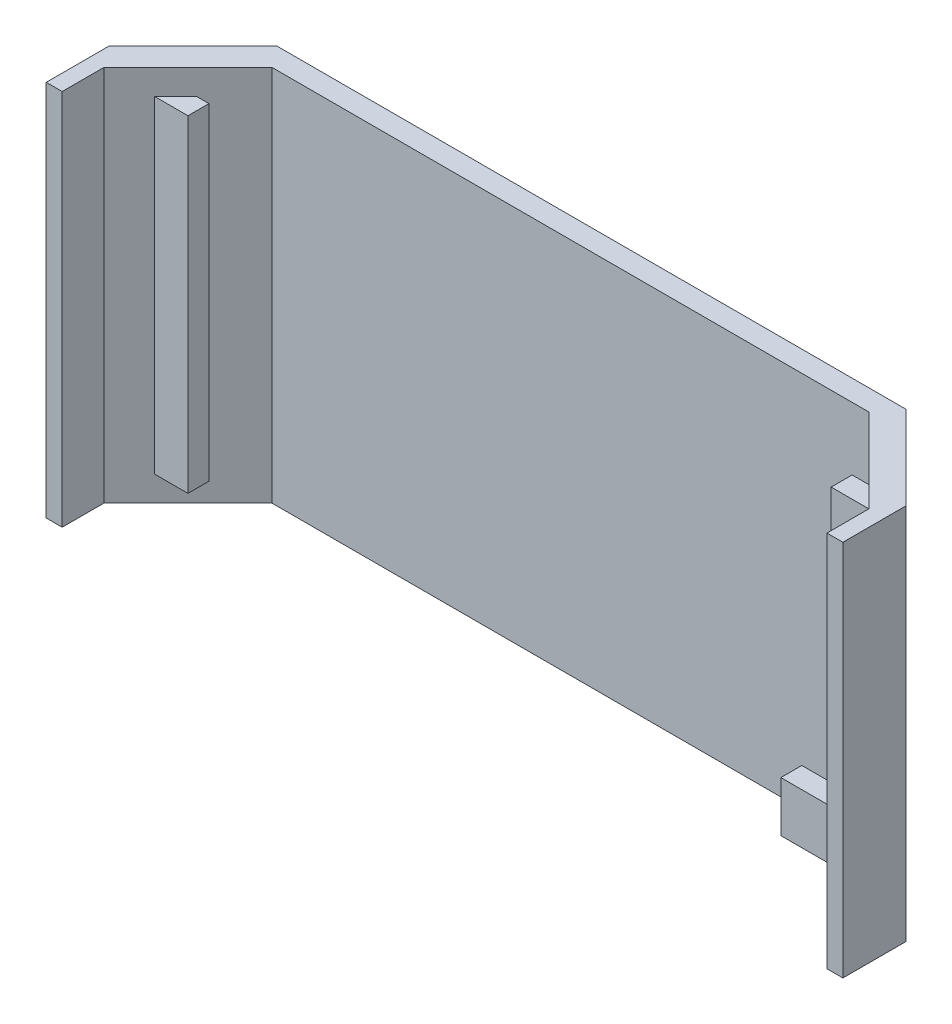
SolidWorks part; units mm, degrees
ref_plane "Front Plane" through (0, 0, 0) normal (0, 0, 1) x (1, 0, 0)
ref_plane "Top Plane" through (0, 0, 0) normal (0, 1, 0) x (1, 0, 0)
ref_plane "Right Plane" through (0, 0, 0) normal (1, 0, 0) x (0, 0, -1)
sketch "Sketch1" plane through (0, 0, 0) normal (0, 0, 1) x (1, 0, 0)
  line L1 (-95, 45) -> (95, 45)
  line L2 (-95, 45) -> (-95, -45)
  line L3 (-95, -45) -> (95, -45)
  line L4 (95, 45) -> (95, -45)
  line L5 (-95, 45) -> (95, -45) construction
  line L6 (-95, -45) -> (95, 45) construction
  point P0 (0, 0)
  point P6 (0, 0)
  dimension "D2" = 190
  dimension "D4" = 90
extrude "Boss-Extrude1" add sketch "Sketch1" along normal blind 5
sketch "Sketch2" plane through (0, 0, 5) normal (0, 0, 1) x (1, 0, 0)
  line L0 (-95, -45) -> (95, -45) construction
  line L1 (-95, 45) -> (-91.2, 45)
  line L2 (-95, 45) -> (-95, -45)
  line L3 (-95, -45) -> (-91.2, -45)
  line L4 (-91.2, 45) -> (-91.2, -45)
  line L5 (0, 0) -> (0, 45) construction
  line L6 (95, 45) -> (-95, 45) construction
  line L7 (95, -45) -> (91.2, -45)
  line L8 (91.2, 45) -> (91.2, -45)
  line L9 (95, 45) -> (91.2, 45)
  line L10 (95, 45) -> (95, -45)
  dimension "D1" = 3.8
extrude "Boss-Extrude2" add sketch "Sketch2" along normal blind 30
sketch "Sketch3" plane through (0, 45, 0) normal (0, 1, 0) x (1, 0, 0)
  line L0 (-91.2, -35) -> (-91.2, -5) construction
  line L1 (-91.2, -14) -> (-77.2, -14)
  line L2 (-91.2, -14) -> (-91.2, -19)
  line L3 (-91.2, -19) -> (-77.2, -19)
  line L4 (-77.2, -14) -> (-77.2, -19)
  line L5 (91.2, -35) -> (91.2, -5) construction
  line L6 (91.2, -14) -> (64.2, -14)
  line L7 (91.2, -14) -> (91.2, -19)
  line L8 (91.2, -19) -> (64.2, -19)
  line L9 (64.2, -14) -> (64.2, -19)
  line L10 (91.2, -5) -> (-91.2, -5) construction
  dimension "D1" = 9
  dimension "D2" = 9
  dimension "D3" = 5
  dimension "D4" = 5
  dimension "D5" = 14
  dimension "D6" = 27
extrude "Boss-Extrude3" add sketch "Sketch3" against normal up to surface (90 mm away) up to face at (0, -45, 18.75)
sketch "Sketch4" plane through (0, 0, 19) normal (0, 0, 1) x (1, 0, 0)
  line L0 (91.2, -45) -> (91.2, 45) construction
  line L1 (-91.2, 45) -> (91.2, 45)
  line L2 (-91.2, 45) -> (-91.2, 39)
  line L3 (-91.2, 39) -> (91.2, 39)
  line L4 (91.2, 45) -> (91.2, 39)
  line L5 (0, 0) -> (-91.2, 0) construction
  line L6 (-91.2, -45) -> (-91.2, 45) construction
  line L7 (-91.2, -39) -> (91.2, -39)
  line L8 (91.2, -45) -> (91.2, -39)
  line L9 (-91.2, -45) -> (91.2, -45)
  line L10 (-91.2, -45) -> (-91.2, -39)
  dimension "D1" = 6
extrude "Cut-Extrude1" cut sketch "Sketch4" against normal blind 5
sketch "Sketch6" plane through (0, 0, 19) normal (0, 0, 1) x (1, 0, 0)
  line L1 (64.2, 39) -> (76.2, 39)
  line L2 (64.2, 39) -> (64.2, -27)
  line L3 (64.2, -27) -> (76.2, -27)
  line L4 (76.2, 39) -> (76.2, -27)
  dimension "D1" = 12
  dimension "D2" = 66
extrude "Cut-Extrude3" cut sketch "Sketch6" against normal up to surface (5 mm away) up to face at (77.7, 0, 14)
chamfer "Chamfer6" distance 20 angle 45 4 edges at (91.2, 0, 5) (95, 0, 0) (-95, 0, 0) (-91.2, 0, 5)
